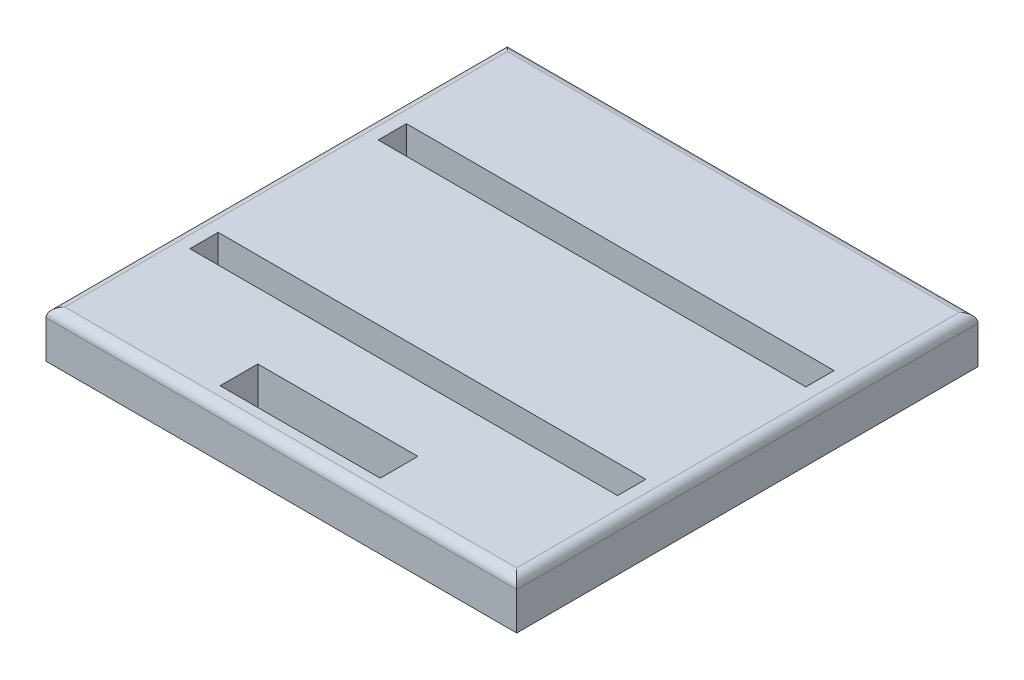
SolidWorks part; units mm, degrees
ref_plane "Front Plane" through (0, 0, 0) normal (0, 0, 1) x (1, 0, 0)
ref_plane "Top Plane" through (0, 0, 0) normal (0, 1, 0) x (1, 0, 0)
ref_plane "Right Plane" through (0, 0, 0) normal (1, 0, 0) x (0, 0, -1)
sketch "Sketch2" plane through (0, 0, 0) normal (0, 1, 0) x (1, 0, 0)
  line L0 (0, 242.4303) -> (0, -237.7501) construction
  line L1 (-63.5, 81.28) -> (-63.5, -43.18)
  line L2 (-63.5, 81.28) -> (63.5, 81.28)
  line L3 (-63.5, -43.18) -> (63.5, -43.18)
  line L4 (63.5, 81.28) -> (63.5, -43.18)
  dimension "D1" = 127
  dimension "D2" = 63.5
  dimension "D3" = 124.46
  dimension "D4" = 43.18
extrude "Boss-Extrude1" add sketch "Sketch2" along normal blind 12.7
fillet "Fillet1" radius 2.54 4 edges at (63.5, 12.7, -19.05) (-63.5, 12.7, -19.05) (0, 12.7, 43.18) (0, 12.7, -81.28)
sketch "Sketch3" plane through (0, 12.7, 0) normal (0, 1, 0) x (1, 0, 0)
  line L0 (57.6928, 40.64) -> (57.6928, 48.26)
  line L1 (57.6928, 40.64) -> (-57.6928, 40.64)
  line L2 (57.6928, 48.26) -> (-57.6928, 48.26)
  line L3 (-57.6928, 40.64) -> (-57.6928, 48.26)
  line L4 (-21.59, -38.1) -> (-21.59, -27.94)
  line L5 (63.5, 81.28) -> (63.5, -43.18) construction
  line L6 (-63.5, 81.28) -> (63.5, 81.28) construction
  line L7 (-60.96, -40.64) -> (60.96, -40.64) construction
  line L8 (-21.59, -27.94) -> (21.59, -27.94)
  line L9 (21.59, -27.94) -> (21.59, -38.1)
  line L10 (57.6928, -2.54) -> (57.6928, -10.16)
  line L11 (57.6928, -10.16) -> (-57.6928, -10.16)
  line L12 (-57.6928, -2.54) -> (-57.6928, -10.16)
  line L13 (57.6928, -2.54) -> (-57.6928, -2.54)
  line L14 (21.59, -38.1) -> (-21.59, -38.1)
  line L17 (60.96, -40.64) -> (60.96, 78.74) construction
  dimension "D1" = 115.3856
  dimension "D2" = 5.8072
  dimension "D3" = 33.02
  dimension "D4" = 7.62
  dimension "D5" = 30.48
  dimension "D6" = 39.37
  dimension "D7" = 43.18
  dimension "D8" = 2.54
  dimension "D9" = 10.16
extrude "Cut-Extrude1" cut sketch "Sketch3" against normal blind 12.7
